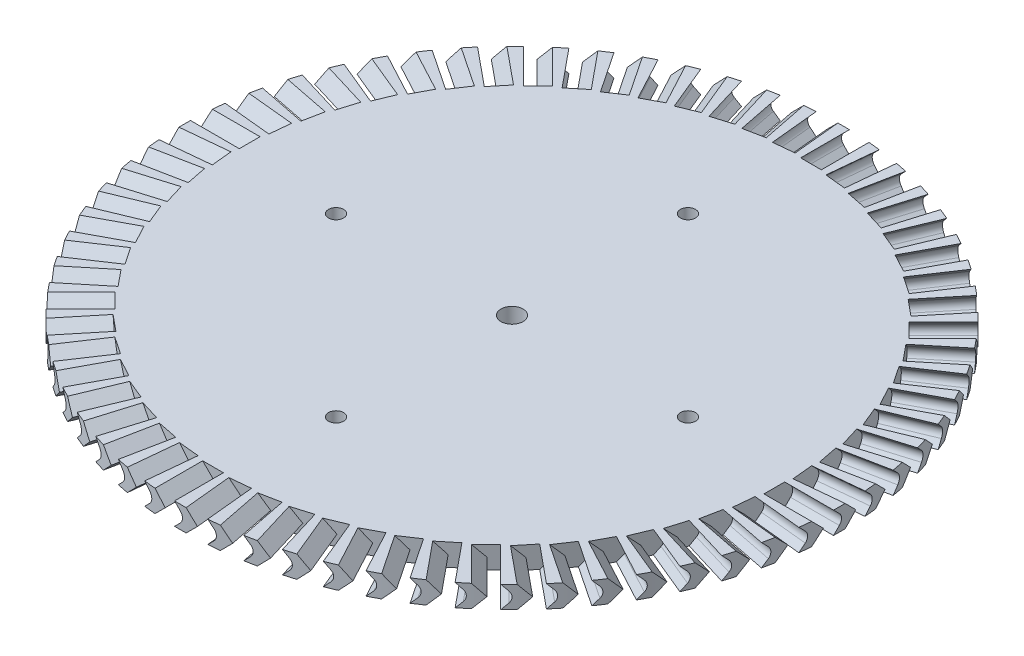
SolidWorks part; units mm, degrees
material "AISI 316 Annealed Stainless Steel Bar (SS)"
ref_plane "Front Plane" through (0, 0, 0) normal (0, 0, 1) x (1, 0, 0)
ref_plane "Top Plane" through (0, 0, 0) normal (0, 1, 0) x (1, 0, 0)
ref_plane "Right Plane" through (0, 0, 0) normal (1, 0, 0) x (0, 0, -1)
sketch "Sketch1" plane through (0, 0, 0) normal (0, 1, 0) x (1, 0, 0)
  circle A0 centre (0, 0) radius 4.7625
  circle A1 centre (0, 0) radius 142.6972
  point P15 (0, 0)
  dimension "D1" = 9.525
  dimension "D2" = 285.3944
extrude "Boss-Extrude1" add sketch "Sketch1" along normal blind 9.525
ref_plane "Plane1" through (0, 0, 142.6972) normal (0, 0, 1) x (1, 0, 0)
sketch "Sketch2" plane through (0, 0, 142.6972) normal (0, 0, 1) x (1, 0, 0)
  line L4 (-0.9299, 2.5174) -> (-3.4474, 0)
  line L5 (-142.6972, 0) -> (142.6972, 0) construction
  line L6 (-0.9299, 7.0076) -> (-3.4474, 9.525)
  line L9 (142.6972, 9.525) -> (-142.6972, 9.525) construction
  line L10 (-5.4201, 2.5174) -> (-12.4276, 9.525)
  line L11 (-5.4201, 7.0076) -> (-12.4276, 0)
  line L12 (-12.4276, 9.525) -> (-3.4474, 9.525)
  line L13 (-12.4276, 0) -> (-3.4474, 0)
  line L14 (0, 0) -> (0, 9.525) construction
  line L15 (4.7625, 9.525) -> (-4.7625, 9.525) construction
  line L16 (-3.175, 4.7625) -> (0, 4.7625) construction
  circle A0 centre (-3.175, 4.7625) radius 3.175
  point P19 (0, 4.7625)
  dimension "D1" = 6.35
  dimension "D2" = 45
  dimension "D3" = 45
extrude "Cut-Extrude1" cut sketch "Sketch2" against normal blind 21.1582 contours A0 | A0 L6 L12 L10 L11 | A0 L11 L10 | A0 L10 L11 L13 L4 region at (-7.2864, 1.5647, 142.6972) region at (-3.175, 4.7625, 142.6972) region at (-6.6622, 4.7625, 142.6972) region at (-7.2864, 7.9603, 142.6972)
pattern_circular "CirPattern1" count 64 over 360 about axis through (0, 9.525, 0) along (0, -1, 0) of "Cut-Extrude1" reverse direction yes
hole_wizard "CBORE for 1/4 Binding Head Machine Screw1" positions "3DSketch1" profile "Sketch3" counterbore size "1/4" standard "ANSI Inch"
sketch3d "3DSketch1"
  line L0 (0, 0, 0) -> (0, 0, 76.2) construction
  point P0 (0, 0, 76.2)
sketch "Sketch3" plane through (0, 0, 76.2) normal (1, 0, 0) x (0, 0, -1)
  line L0 (0, 0) -> (0, 14.6611)
  line L1 (0, 14.6611) -> (3.2639, 12.7)
  line L2 (3.2639, 12.7) -> (3.2639, 4.191)
  line L3 (3.2639, 4.191) -> (7.1437, 4.191)
  line L4 (7.1437, 4.191) -> (7.1437, 0)
  line L5 (7.1437, 0) -> (0, 0)
  line L10 (0, 14.6611) -> (-3.2639, 12.7) construction
  line L11 (0, -6.35) -> (0, 107.95) construction
  dimension "Hole Dia." = 6.5278
  dimension "Hole Depth" = 12.7
  dimension "C'Bore Dia." = 14.2875
  dimension "C'Bore Depth" = 4.191
  dimension "Drill Angle" = 118
pattern_circular "CirPattern2" count 4 over 360 about axis through (0, 9.525, 0) along (0, -1, 0) of "CBORE for 1/4 Binding Head Machine Screw1"
